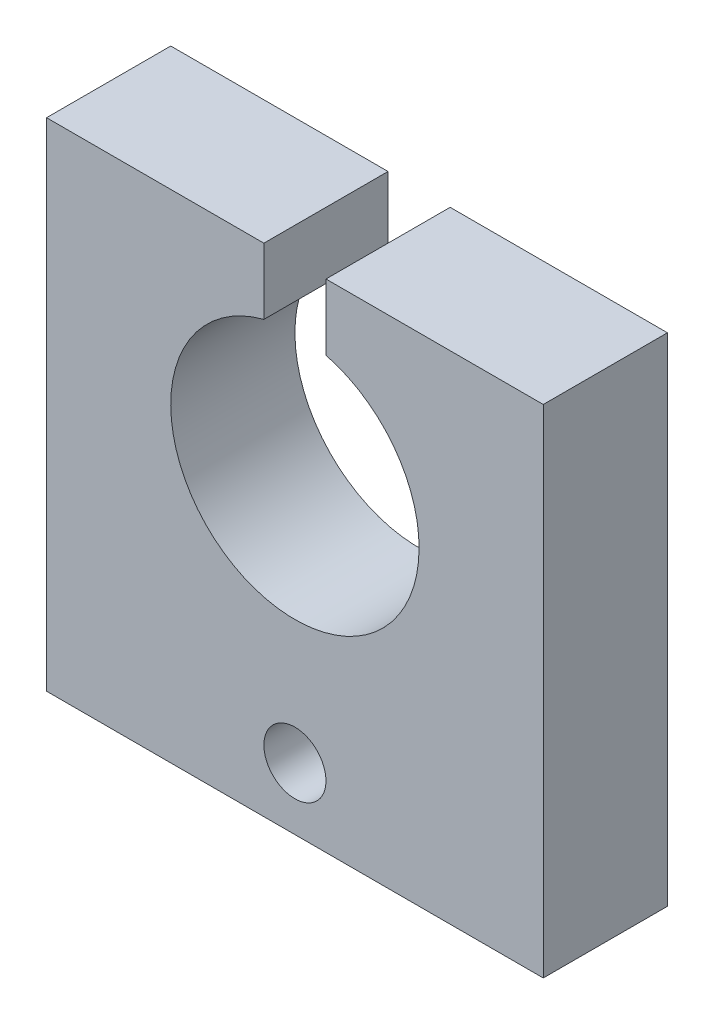
SolidWorks part; units mm, degrees
material "6061 Alloy"
ref_plane "Front Plane" through (0, 0, 0) normal (0, 0, 1) x (1, 0, 0)
ref_plane "Top Plane" through (0, 0, 0) normal (0, 1, 0) x (1, 0, 0)
ref_plane "Right Plane" through (0, 0, 0) normal (1, 0, 0) x (0, 0, -1)
sketch "Sketch1" plane through (0, 0, 0) normal (0, 0, 1) x (1, 0, 0)
  line L1 (-12.7, -12.7) -> (12.7, -12.7)
  line L2 (-12.7, -12.7) -> (-12.7, 12.7)
  line L3 (-12.7, 12.7) -> (12.7, 12.7)
  line L4 (12.7, -12.7) -> (12.7, 12.7)
  line L5 (-12.7, -12.7) -> (12.7, 12.7) construction
  line L6 (-12.7, 12.7) -> (12.7, -12.7) construction
  point P0 (0, 0)
  dimension "D1" = 25.4
  dimension "D2" = 25.4
extrude "Boss-Extrude1" add sketch "Sketch1" along normal blind 6.35
sketch "Sketch2" plane through (0, 0, 6.35) normal (0, 0, 1) x (1, 0, 0)
  line L1 (-1.5875, 1.7402) -> (1.5875, 1.7402)
  line L2 (-1.5875, 1.7402) -> (-1.5875, 12.7)
  line L3 (-1.5875, 12.7) -> (1.5875, 12.7)
  line L4 (1.5875, 1.7402) -> (1.5875, 12.7)
  line L5 (12.7, 12.7) -> (-12.7, 12.7) construction
  circle A0 centre (0, 3.175) radius 6.35
  line M4 (12.7, 12.7) -> (-12.7, 12.7)
  dimension "D2" = 12.7
  dimension "D1" = 3.175
  dimension "D3" = 1.5875
  dimension "D4" = 3.175
  dimension "D5" = 0
  dimension "D6" = 0
extrude "Cut-Extrude1" cut sketch "Sketch2" against normal through all contours L2 A0 L4 L1 | L4 A0 L2 L1 | A0 L4 L2 M4 region at (0, 5.5994, 6.35) region at (0, 1.562, 6.35) region at (0, 11.0786, 6.35)
sketch "Sketch3" plane through (0, 0, 6.35) normal (0, 0, 1) x (1, 0, 0)
  line L0 (-12.7, -12.7) -> (12.7, -12.7) construction
  circle A0 centre (0, -9.525) radius 1.5875
  dimension "D1" = 3.175
  dimension "D2" = 3.175
extrude "Cut-Extrude2" cut sketch "Sketch3" against normal through all
